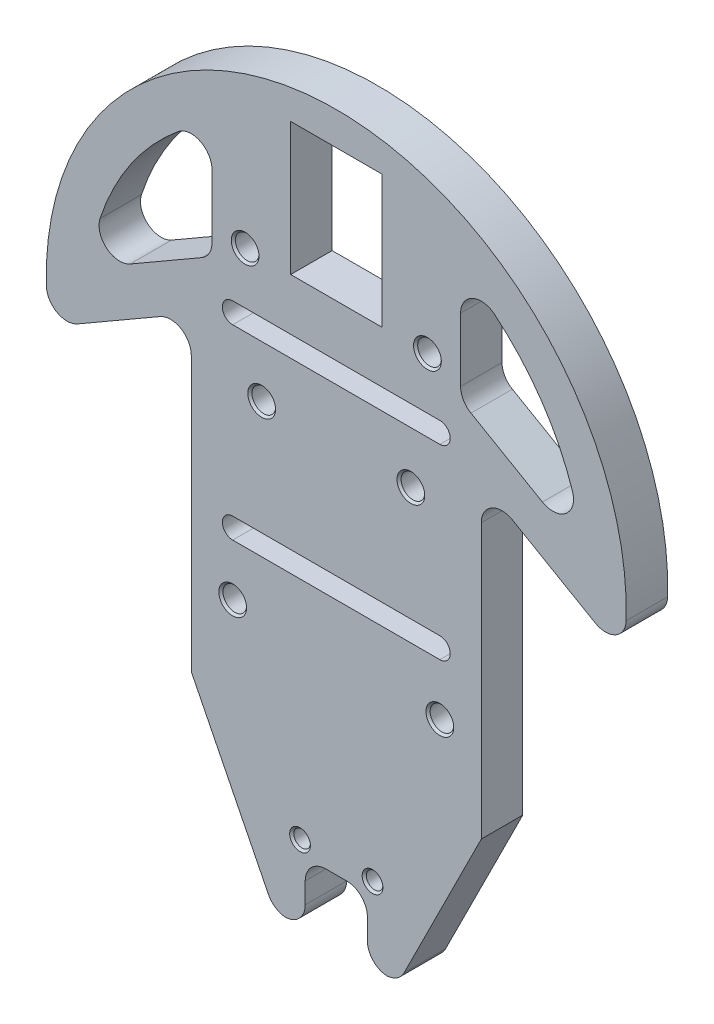
SolidWorks part; units mm, degrees
material "ABS PC"
ref_plane "Front Plane" through (0, 0, 0) normal (0, 0, 1) x (1, 0, 0)
ref_plane "Top Plane" through (0, 0, 0) normal (0, 1, 0) x (1, 0, 0)
ref_plane "Right Plane" through (0, 0, 0) normal (1, 0, 0) x (0, 0, -1)
sketch "Sketch4" plane through (0, 0, 0) normal (0, 0, 1) x (1, 0, 0)
  line L0 (0, 0) -> (0, -50000) construction
  line L1 (-69.282, -10) -> (-35, 9.7927)
  line L2 (-35, -105) -> (35, -105)
  line L3 (-35, -105) -> (-35, 9.7927)
  line L5 (35, -105) -> (35, 9.7927)
  line L6 (69.282, -10) -> (35, 9.7927)
  line L7 (-59.5721, 7.153) -> (-30, 24.2265)
  line L9 (-30, 24.2265) -> (-30, 51.9615)
  line L10 (30, 24.2265) -> (30, 51.9615)
  line L11 (59.5721, 7.153) -> (30, 24.2265)
  line L12 (0, -10) -> (50000, -10) construction
  line L13 (-35, -65) -> (-15, -105)
  line L14 (35, -65) -> (15, -105)
  line L17 (-35, -65) -> (-35, -55)
  line L23 (-25, -32.5) -> (25, -32.5)
  line L24 (-25, -27.5) -> (25, -27.5)
  line L25 (-11, 30) -> (11, 30)
  line L26 (-25, 12.5) -> (25, 12.5)
  line L27 (11, 30) -> (11, 62)
  line L28 (11, 62) -> (-11, 62)
  line L29 (-11, 62) -> (-11, 30)
  line L31 (-25, 17.5) -> (25, 17.5)
  line L32 (-7.5, -105) -> (7.5, -105)
  line L33 (-7.5, -105) -> (-7.5, -90)
  line L34 (-7.5, -90) -> (7.5, -90)
  line L35 (7.5, -105) -> (7.5, -90)
  arc A0 (-69.282, -10) -> (69.282, -10) centre (0, 0) cw
  arc A1 (-59.5721, 7.153) -> (-30, 51.9615) centre (0, 0) cw
  arc A2 (59.5721, 7.153) -> (30, 51.9615) centre (0, 0) ccw
  circle A3 centre (-25, -45) radius 2.85
  circle A4 centre (-18, 0) radius 2.85
  circle A5 centre (-22, 30) radius 2.85
  circle A6 centre (-8.75, -87) radius 2
  circle A7 centre (8.75, -87) radius 2
  circle A8 centre (25, -45) radius 2.85
  circle A9 centre (18, 0) radius 2.85
  circle A10 centre (22, 30) radius 2.85
  arc A14 (-25, -32.5) -> (-25, -27.5) centre (-25, -30) cw
  arc A15 (25, -32.5) -> (25, -27.5) centre (25, -30) ccw
  arc A16 (-25, 12.5) -> (-25, 17.5) centre (-25, 15) cw
  arc A17 (25, 12.5) -> (25, 17.5) centre (25, 15) ccw
  point P7 (0, -105)
  point P12 (0, 70)
  point P48 (0, 12.5)
  point P58 (0, -32.5)
  dimension "D3" = 10
  dimension "D4" = 30
  dimension "D5" = 70
  dimension "D1" = 10
  dimension "D9" = 60
  dimension "D12" = 5.7
  dimension "D15" = 8.75
  dimension "D16" = 4
  dimension "D17" = 18
  dimension "D20" = 15
  dimension "D22" = 50
  dimension "D23" = 2.5
  dimension "D2" = 70
  dimension "D6" = 60
  dimension "D7" = 105
  dimension "D8" = 10
  dimension "D10" = 45
  dimension "D11" = 22
  dimension "D13" = 25
  dimension "D14" = 30
  dimension "D18" = 20
  dimension "D19" = 40
  dimension "D21" = 18
  dimension "D24" = 15
  dimension "D25" = 22
  dimension "D26" = 32
  dimension "D27" = 11
  dimension "D28" = 15
  dimension "D29" = 15
  dimension "D30" = 7.5
extrude "Boss-Extrude1" add sketch "Sketch4" along normal mid plane 10 contours L2 L34 L14 L5 L6 A0 L1 L3 L13 A9 A7 A6 A5 A4 A3 A2 L11 L10 L7 A1 L9 A8 A10 region at (0, -11.0664, 0)
fillet "Fillet1" radius 5 16 edges at (59.5721, 7.153, 0) (30, 24.2265, 0) (30, 51.9615, 0) (-59.5721, 7.153, 0) (-30, 24.2265, 0) (-30, 51.9615, 0) (35, 9.7927, 0) (-35, 9.7927, 0) (-69.282, -10, 0) (69.282, -10, 0) (15, -105, 0) (-15, -105, 0) (7.5, -105, 0) (7.5, -90, 0) (-7.5, -90, 0) (-7.5, -105, 0)
chamfer "Chamfer1" distance 0.5 angle 45 8 edges at (20.85, 0, 5) (27.85, -45, 5) (-22.15, -45, 5) (-15.15, 0, 5) (24.85, 30, 5) (-19.15, 30, 5) (10.75, -87, 5) (-6.75, -87, 5)
